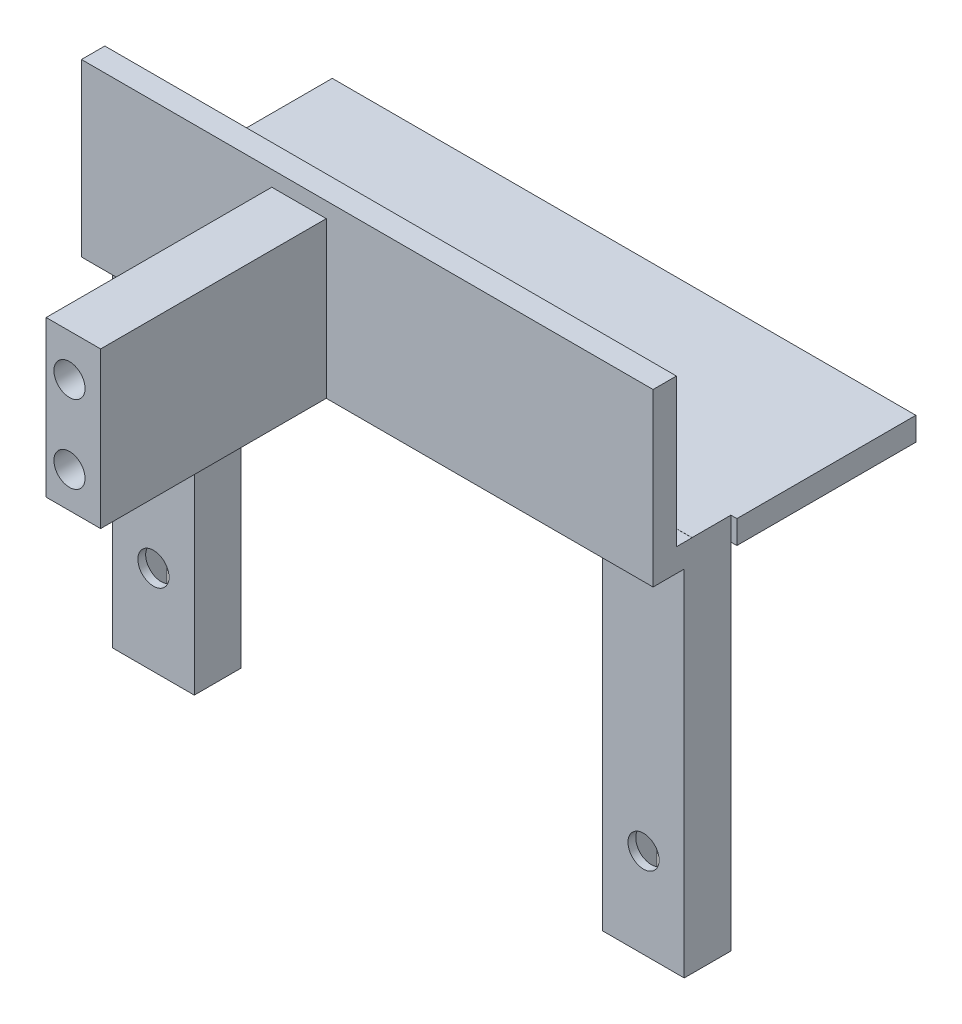
SolidWorks part; units mm, degrees
ref_plane "Front Plane" through (0, 0, 0) normal (0, 0, 1) x (1, 0, 0)
ref_plane "Top Plane" through (0, 0, 0) normal (0, 1, 0) x (1, 0, 0)
ref_plane "Right Plane" through (0, 0, 0) normal (1, 0, 0) x (0, 0, -1)
sketch "Sketch1" plane through (0, 0, 0) normal (0, 1, 0) x (1, 0, 0)
  line L1 (-37.5, -11.5) -> (37.5, -11.5)
  line L2 (-37.5, -11.5) -> (-37.5, 11.5)
  line L3 (-37.5, 11.5) -> (37.5, 11.5)
  line L4 (37.5, -11.5) -> (37.5, 11.5)
  line L5 (-37.5, -11.5) -> (37.5, 11.5) construction
  line L6 (-37.5, 11.5) -> (37.5, -11.5) construction
  point P0 (0, 0)
extrude "Boss-Extrude1" add sketch "Sketch1" along normal blind 3
sketch "Sketch2" plane through (0, 0, 11.5) normal (0, 0, 1) x (1, 0, 0)
  line L3 (27.2303, 0) -> (27.2303, -45.5149)
  line L5 (-35.4803, -45.5149) -> (-37.4966, -45.5149) construction
  line L7 (-12.4738, -45.5149) -> (-27.4803, -45.5149) construction
  line L14 (-35.7303, -45.5149) -> (-36.7303, -45.5149)
  line L15 (-27.2303, -45.5149) -> (-26.2303, -45.5149)
  line L16 (-26.2303, -45.5149) -> (-26.2303, 3)
  line L17 (-37.5, 3) -> (37.5, 3) construction
  line L19 (-26.2303, 3) -> (-36.7303, 3)
  line L20 (-36.7303, 3) -> (-36.7303, -45.5149)
  line L22 (-35.7303, -45.5149) -> (-35.7303, 0)
  line L23 (-37.5, 0) -> (37.5, 0) construction
  line L24 (-35.7303, 0) -> (-27.2303, 0)
  line L25 (-27.2303, 0) -> (-27.2303, -45.5149)
  line L26 (35.7303, 0) -> (27.2303, 0)
  line L27 (35.7303, -45.5149) -> (35.7303, 0)
  line L28 (36.7303, 3) -> (36.7303, -45.5149)
  line L29 (26.2303, 3) -> (36.7303, 3)
  line L30 (26.2303, -45.5149) -> (26.2303, 3)
  line L31 (27.2303, -45.5149) -> (26.2303, -45.5149)
  line L32 (35.7303, -45.5149) -> (36.7303, -45.5149)
extrude "Boss-Extrude4" add sketch "Sketch2" along normal blind 5
sketch "Sketch3" plane through (0, -45.5149, 0) normal (0, -1, 0) x (1, 0, 0)
  line L0 (-36.7303, 16.5) -> (-26.2303, 16.5)
  line L1 (-26.2303, 16.5) -> (-26.2303, 17.5)
  line L2 (-26.2303, 17.5) -> (-36.7303, 17.5)
  line L3 (-36.7303, 17.5) -> (-36.7303, 16.5)
  line L4 (26.2303, 16.5) -> (36.7303, 16.5)
  line L5 (36.7303, 16.5) -> (36.7303, 17.5)
  line L6 (36.7303, 17.5) -> (26.2303, 17.5)
  line L7 (26.2303, 17.5) -> (26.2303, 16.5)
extrude "Boss-Extrude5" add sketch "Sketch3" against normal blind 48.5
sketch "Sketch4" plane through (0, 0, 16.5) normal (0, 0, -1) x (-1, 0, 0)
  circle A0 centre (31.4813, -34.0121) radius 2
  circle A1 centre (-31.5034, -34.0149) radius 2
extrude "Cut-Extrude1" cut sketch "Sketch4" against normal through all
sketch "Sketch8" plane through (0, 0, 11.5) normal (0, 0, 1) x (1, 0, 0)
  line L1 (-36.7303, 2.9851) -> (36.7303, 2.9851)
  line L2 (-36.7303, 2.9851) -> (-36.7303, 0)
  line L3 (-36.7303, 0) -> (36.7303, 0)
  line L4 (36.7303, 2.9851) -> (36.7303, 0)
extrude "Boss-Extrude9" add sketch "Sketch8" along normal blind 10
sketch "Sketch12" plane through (0, 2.9851, 0) normal (0, 1, 0) x (1, 0, 0)
  line L0 (36.7303, -18.5) -> (47.827, -18.5) construction
  line L1 (36.7303, -16.5) -> (36.7303, -21.5) construction
  line L2 (47.827, -18.5) -> (-50.2663, -18.5) construction
  line L3 (36.7303, -21.5) -> (-36.7303, -21.5) construction
  line L5 (-36.7303, -21.5) -> (36.7303, -21.5)
  line L6 (-36.7303, -21.5) -> (-36.7303, -18.5)
  line L7 (-36.7303, -18.5) -> (36.7303, -18.5)
  line L8 (36.7303, -21.5) -> (36.7303, -18.5)
  dimension "D1" = 3
extrude "Boss-Extrude10" add sketch "Sketch12" along normal blind 19
sketch "Sketch13" plane through (0, 0, 21.5) normal (0, 0, 1) x (1, 0, 0)
  line L0 (-36.7303, 0) -> (36.7303, 0) construction
  line L1 (-12.2697, 0) -> (-5.2697, 0)
  line L2 (-12.2697, 0) -> (-12.2697, 20)
  line L3 (-12.2697, 20) -> (-5.2697, 20)
  line L4 (-5.2697, 0) -> (-5.2697, 20)
  line L5 (36.7303, 0) -> (36.7303, 21.9851) construction
  dimension "D1" = 42
  dimension "D2" = 20
  dimension "D3" = 7
extrude "Boss-Extrude11" add sketch "Sketch13" along normal blind 29
sketch "Sketch14" plane through (0, 0, 50.5) normal (0, 0, 1) x (1, 0, 0)
  line L0 (-9.2697, 20) -> (-9.2697, 25.7375) construction
  line L1 (-5.2697, 20) -> (-12.2697, 20) construction
  line L2 (-9.2697, 25.7375) -> (-9.2697, -6.6243) construction
  line L3 (-5.2697, 0) -> (-5.2697, 20) construction
  line L4 (-5.2697, 20) -> (-12.2697, 20) construction
  line L5 (-12.2697, 0) -> (-5.2697, 0) construction
  circle A0 centre (-9.2697, 14.59) radius 2
  circle A1 centre (-9.2697, 4.59) radius 2
  dimension "D2" = 4
  dimension "D3" = 4
  dimension "D1" = 4
  dimension "D4" = 5.41
  dimension "D5" = 4.59
extrude "Cut-Extrude2" cut sketch "Sketch14" against normal blind 10
